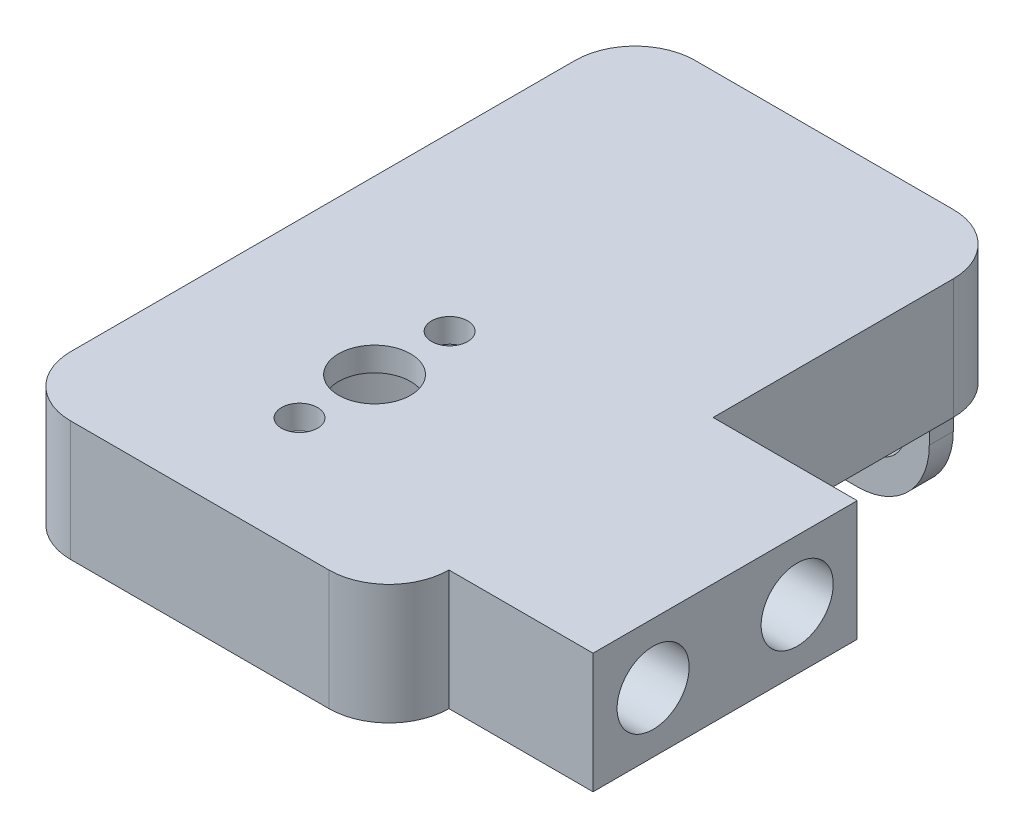
SolidWorks part; units mm, degrees
ref_plane "Front Plane" through (0, 0, 0) normal (0, 0, 1) x (1, 0, 0)
ref_plane "Top Plane" through (0, 0, 0) normal (0, 1, 0) x (1, 0, 0)
ref_plane "Right Plane" through (0, 0, 0) normal (1, 0, 0) x (0, 0, -1)
sketch "Sketch1" plane through (0, 0, 0) normal (0, 1, 0) x (1, 0, 0)
  line L0 (5.5, 11) -> (5.5, 36)
  line L1 (5.5, 11) -> (17.5, 11)
  line L3 (5.5, -11) -> (17.5, -11)
  line L4 (17.5, 11) -> (17.5, -11)
  line L5 (0, 0) -> (17.5, -11) construction
  line L6 (0, 0) -> (17.5, 11) construction
  line L7 (5.5, 36) -> (-26, 36)
  line L8 (-26, 36) -> (-26, -16)
  line L9 (-26, -16) -> (5.5, -16)
  line L10 (5.5, -16) -> (5.5, -11)
  point P0 (0, 0)
  dimension "D1" = 22
  dimension "D2" = 12
  dimension "D3" = 12
  dimension "D4" = 16
  dimension "D5" = 25
  dimension "D6" = 26
extrude "Boss-Extrude1" add sketch "Sketch1" along normal blind 10
sketch "Sketch2" plane through (17.5, 0, 0) normal (1, 0, 0) x (0, 0, -1)
  line L0 (-11, 0) -> (11, 0) construction
  line L1 (-11, 10) -> (-11, 0) construction
  line L2 (11, 10) -> (11, 0) construction
  circle A0 centre (-6, 5) radius 3
  circle A1 centre (6, 5) radius 3
  dimension "D1" = 5
  dimension "D2" = 5
  dimension "D3" = 5
  dimension "D4" = 5
extrude "Cut-Extrude1" cut sketch "Sketch2" against normal blind 10
sketch "Sketch4" plane through (0, 0, 0) normal (0, -1, 0) x (1, 0, 0)
  circle A0 centre (-11.6955, 0) radius 11
extrude "Cut-Extrude3" cut sketch "Sketch4" against normal blind 8
sketch "Sketch5" plane through (0, 8, 0) normal (0, -1, 0) x (-1, 0, 0)
  circle A0 centre (11.6955, 0) radius 3
  circle A1 centre (11.6955, -6.25) radius 1.5
  circle A2 centre (11.6955, 6.25) radius 1.5
  dimension "D1" = 6.25
  dimension "D2" = 3
  dimension "D3" = 6.25
extrude "Cut-Extrude4" cut sketch "Sketch5" against normal blind 8
fillet "Fillet1" radius 5 4 edges at (-26, 5, -36) (5.5, 5, -36) (5.5, 5, 16) (-26, 5, 16)
sketch "Sketch6" plane through (0, 0, 0) normal (0, -1, 0) x (1, 0, 0)
  line L1 (-21, -36) -> (-21, -34)
  line L2 (0.5, -36) -> (0.5, -34)
  line L3 (0.5, -34) -> (-21, -34)
  line L4 (-21, -36) -> (0.5, -36)
  dimension "D2" = 2
  dimension "D3" = 2
extrude "Boss-Extrude2" add sketch "Sketch6" along normal blind 12
sketch "Sketch7" plane through (0, 0, -34) normal (0, 0, 1) x (1, 0, 0)
  line L0 (-21, -12) -> (-21, 0) construction
  line L1 (0.5, -12) -> (0.5, 0) construction
  line L2 (0.5, -12) -> (-21, -12) construction
  circle A0 centre (-16, -6) radius 3
  circle A1 centre (-4.5, -6) radius 3
  dimension "D1" = 6
  dimension "D2" = 6
  dimension "D3" = 5
  dimension "D4" = 5
  dimension "D5" = 6
  dimension "D6" = 6
extrude "Cut-Extrude5" cut sketch "Sketch7" against normal blind 12
fillet "Fillet2" radius 6 2 edges at (-21, -12, -35) (0.5, -12, -35)
